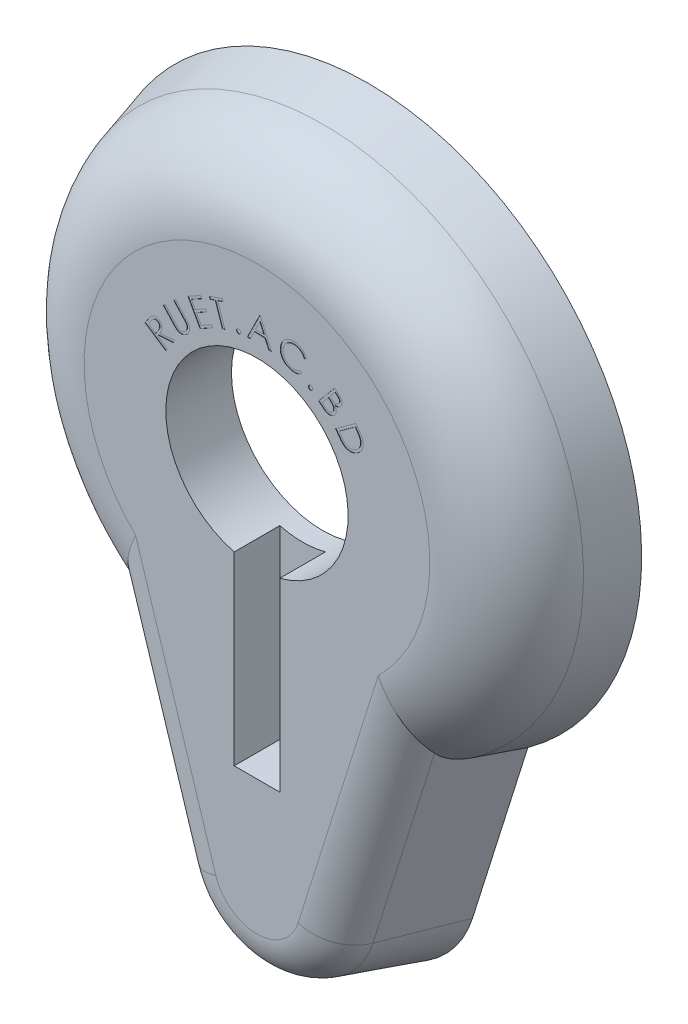
SolidWorks part; units mm, degrees
material "Brass"
ref_plane "Front Plane" through (0, 0, 0) normal (0, 0, 1) x (1, 0, 0)
ref_plane "Top Plane" through (0, 0, 0) normal (0, 1, 0) x (1, 0, 0)
ref_plane "Right Plane" through (0, 0, 0) normal (1, 0, 0) x (0, 0, -1)
sketch "Sketch1" plane through (0, 0, 0) normal (0, 0, 1) x (1, 0, 0)
  line L0 (0, 0) -> (0, -77.026) construction
  line L1 (0, 0) -> (0, 50.8) construction
  line L4 (-14.5346, -4.5828) -> (-22.2438, 19.8674)
  line L5 (14.5346, -4.5828) -> (22.2438, 19.8674)
  arc A8 (14.5346, -4.5828) -> (-14.5346, -4.5828) centre (0, 0) cw
  arc A9 (-22.2438, 19.8674) -> (22.2438, 19.8674) centre (0, 50.8) cw
  dimension "D1" = 15.24
  dimension "D2" = 38.1
  dimension "D3" = 50.8
  dimension "D4" = 35
sketch "Sketch3" plane through (0, 0, 0) normal (0, 0, 1) x (1, 0, 0)
extrude "Boss-Extrude2" add sketch "Sketch1" along normal blind 15.494 draft 16
fillet "Fillet1" radius 6.35 3 edges at (14.3818, 9.7071, 15.494) (0, -10.7972, 15.494) (-14.3818, 9.7071, 15.494)
fillet "Fillet2" radius 12.7 1 edges at (0, 84.4572, 15.494)
sketch "Sketch4" plane through (0, 0, 0) normal (0, 0, -1) x (-1, 0, 0)
  line L4 (12.1122, -3.819) -> (20.0801, 21.4521)
  line L5 (-20.0801, 21.4521) -> (-12.1122, -3.819)
  line L6 (12.1122, -3.819) -> (20.0801, 21.4521)
  line L7 (-20.0801, 21.4521) -> (-12.1122, -3.819)
  arc A4 (-12.1122, -3.819) -> (12.1122, -3.819) centre (0, 0) ccw
  arc A5 (20.0801, 21.4521) -> (-20.0801, 21.4521) centre (0, 50.8) ccw
  arc A6 (-12.1122, -3.819) -> (12.1122, -3.819) centre (0, 0) ccw
  arc A7 (20.0801, 21.4521) -> (-20.0801, 21.4521) centre (0, 50.8) ccw
  dimension "D1" = 2.54
extrude "Cut-Extrude1" cut sketch "Sketch4" against normal blind 6.35 draft 16
sketch "Sketch5" plane through (0, 0, 15.494) normal (0, 0, 1) x (1, 0, 0)
  circle A0 centre (0, 50.8) radius 12.7
  arc A1 (16.9138, 33.6504) -> (-16.9138, 33.6504) centre (0, 50.8) ccw construction
  dimension "D1" = 25.4
extrude "Cut-Extrude4" cut sketch "Sketch5" against normal through all contours A0
sketch "Sketch10" plane through (0, 0, 15.494) normal (0, 0, 1) x (1, 0, 0)
  line L0 (0, 12.7) -> (0, 0) construction
  line L1 (-3.175, 58.42) -> (3.175, 58.42)
  line L2 (-3.175, 58.42) -> (-3.175, 12.7)
  line L3 (-3.175, 12.7) -> (3.175, 12.7)
  line L4 (3.175, 58.42) -> (3.175, 12.7)
  point P6 (0, 6.35)
  dimension "D1" = 6.35
  dimension "D2" = 45.72
  dimension "D3" = 6.35
extrude "Cut-Extrude9" cut sketch "Sketch10" against normal blind 6.35 contours L1 L4 L3 L2
sketch "Sketch11" plane through (0, 0, 15.494) normal (0, 0, 1) x (1, 0, 0)
  arc A0 (-12.9364, 57.6524) -> (12.7465, 57.9996) centre (0, 50.8) cw construction
  text T0 "RUET.AC.BD"
extrude "Cut-Extrude10" cut sketch "Sketch11" against normal blind 0.0508
